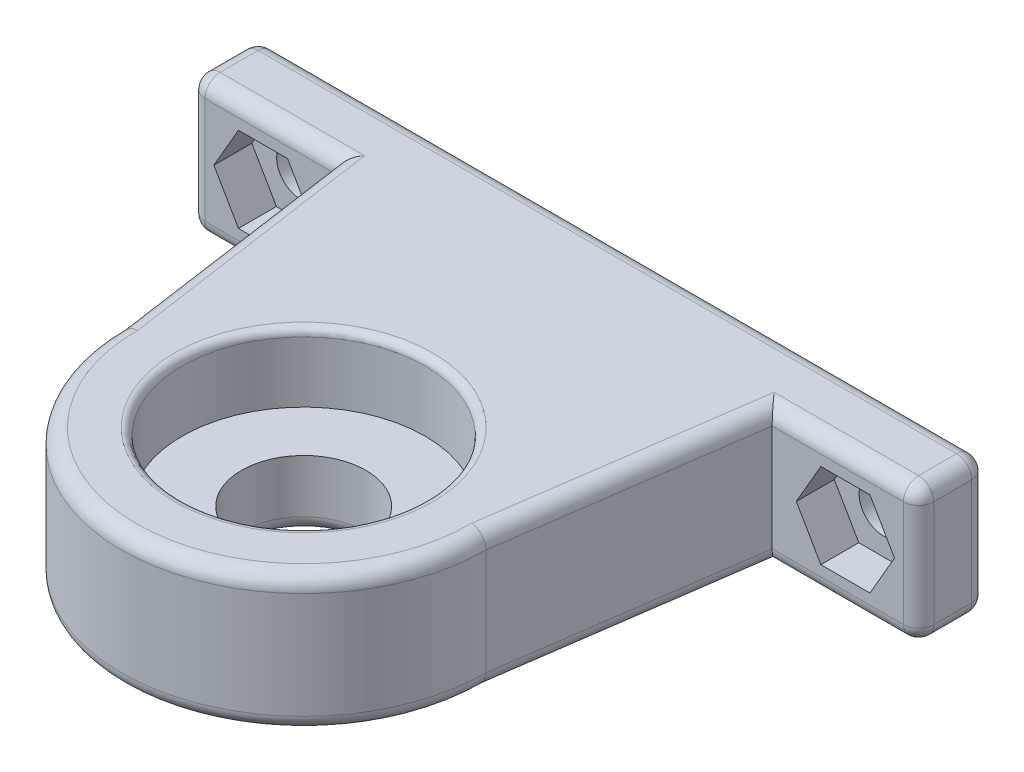
SolidWorks part; units mm, degrees
ref_plane "Alzado" through (0, 0, 0) normal (0, 0, 1) x (1, 0, 0)
ref_plane "Planta" through (0, 0, 0) normal (0, 1, 0) x (1, 0, 0)
ref_plane "Vista lateral" through (0, 0, 0) normal (1, 0, 0) x (0, 0, -1)
sketch "Croquis1" plane through (0, 0, 0) normal (0, 1, 0) x (1, 0, 0)
  line L0 (-12.5027, 9.6432) -> (-10.1455, -6.8568)
  line L1 (-13.1455, 14.1432) -> (16.8545, 14.1432)
  line L2 (1.8545, -6.8568) -> (1.8545, 30.0374) construction
  line L3 (-13.1455, 14.1432) -> (-20.1455, 14.1432)
  line L4 (16.8545, 9.6432) -> (16.2116, 9.6432)
  line L5 (-13.1455, 9.6432) -> (-20.1455, 9.6432)
  line L6 (16.2116, 9.6432) -> (13.8545, -6.8568)
  line L8 (-13.1455, 9.6432) -> (-12.5027, 9.6432)
  line L9 (16.8545, 14.1432) -> (23.8545, 14.1432)
  line L11 (16.8545, 9.6432) -> (23.8545, 9.6432)
  line L12 (23.8545, 14.1432) -> (25.8545, 14.1432)
  line L13 (-20.1455, 14.1432) -> (-22.1455, 14.1432)
  line L15 (-20.1455, 9.6432) -> (-22.1455, 9.6432)
  line L16 (-22.1455, 14.1432) -> (-22.1455, 9.6432)
  line L17 (23.8545, 9.6432) -> (25.8545, 9.6432)
  line L18 (25.8545, 14.1432) -> (25.8545, 9.6432)
  circle A0 centre (1.8545, -6.8568) radius 8
  circle A1 centre (1.8545, -6.8568) radius 12
  circle A2 centre (1.8545, -6.8568) radius 4.1
  dimension "D3" = 16
  dimension "D7" = 2
  dimension "D1" = 30
  dimension "D2" = 21
  dimension "D5" = 7
  dimension "D6" = 4.5
  dimension "D8" = 2
  dimension "D4" = 4
extrude "Saliente-Extruir2" add sketch "Croquis1" along normal blind 9 contours A0 A1 | A2 A0 | A1 L2 L1 L3 L5 L8 L0 | L2 A1 L6 L4 L11 L9 L1 region at (-8.3016, 0, -8.6667) region at (7.3513, 0, 1.36) region at (-6.3908, 0, -1.3885) region at (12.0105, 0, -8.6667)
sketch "Croquis2" plane through (0, 9, 0) normal (0, 1, 0) x (1, 0, 0)
  circle A0 centre (1.8545, -6.8568) radius 4.1 construction
  circle A1 centre (1.8545, -6.8568) radius 4.1
  circle A2 centre (1.8545, -6.8568) radius 8
extrude "Cortar-Extruir1" cut sketch "Croquis2" against normal blind 4.5
sketch "Croquis3" plane through (0, 0, -9.6432) normal (0, 0, 1) x (1, 0, 0)
  line L0 (-12.5027, 9) -> (-22.1455, 0) construction
  line L2 (-14.0909, 4.5) -> (-15.7075, 7.3)
  line L3 (-15.7075, 7.3) -> (-18.9407, 7.3)
  line L12 (-18.9407, 7.3) -> (-20.5573, 4.5)
  line L13 (-20.5573, 4.5) -> (-18.9407, 1.7)
  line L14 (-18.9407, 1.7) -> (-15.7075, 1.7)
  line L15 (-15.7075, 1.7) -> (-14.0909, 4.5)
  circle A0 centre (-17.3241, 4.5) radius 2.8 construction
  dimension "D2" = 5.6
extrude "Cortar-Extruir3" cut sketch "Croquis3" against normal blind 2.5
sketch "Croquis4" plane through (0, 0, -9.6432) normal (0, 0, 1) x (1, 0, 0)
  line L0 (25.8545, 9) -> (16.2116, 0) construction
  line L1 (16.2116, 9) -> (16.2116, 0) construction
  line L2 (25.8545, 0) -> (16.2116, 0) construction
  line L4 (24.2662, 4.5) -> (22.6496, 7.3)
  line L5 (22.6496, 7.3) -> (19.4165, 7.3)
  line L6 (19.4165, 7.3) -> (17.7999, 4.5)
  line L7 (17.7999, 4.5) -> (19.4165, 1.7)
  line L8 (19.4165, 1.7) -> (22.6496, 1.7)
  line L9 (22.6496, 1.7) -> (24.2662, 4.5)
  circle A0 centre (21.033, 4.5) radius 2.8 construction
  dimension "D1" = 5.6
extrude "Cortar-Extruir4" cut sketch "Croquis4" against normal blind 2.5
sketch "Croquis5" plane through (0, 0, -12.1432) normal (0, 0, 1) x (1, 0, 0)
  line L0 (17.7999, 4.5) -> (24.2662, 4.5) construction
  line L1 (-20.5573, 4.5) -> (-14.0909, 4.5) construction
  circle A0 centre (21.033, 4.5) radius 1.6
  circle A1 centre (-17.3241, 4.5) radius 1.6
extrude "Cortar-Extruir5" cut sketch "Croquis5" against normal blind 2.5
fillet "Redondeo1" radius 1 21 edges at (1.8545, 0, 10.9568) (-17.3241, 0, -9.6432) (-11.3241, 0, -1.3932) (1.8545, 0, 18.8568) (15.033, 0, -1.3932) (21.033, 0, -9.6432) (1.8545, 0, -14.1432) (21.033, 9, -9.6432) (15.033, 9, -1.3932) (1.8545, 9, 18.8568) (-11.3241, 9, -1.3932) (-17.3241, 9, -9.6432) (1.8545, 9, -14.1432) (25.8545, 9, -11.8932) (-22.1455, 9, -11.8932) (-22.1455, 0, -11.8932) (25.8545, 0, -11.8932) (-22.1455, 4.5, -9.6432) (-22.1455, 4.5, -14.1432) (25.8545, 4.5, -9.6432) (25.8545, 4.5, -14.1432)
fillet "Redondeo2" radius 0.5 1 edges at (1.8545, 9, 14.8568)
